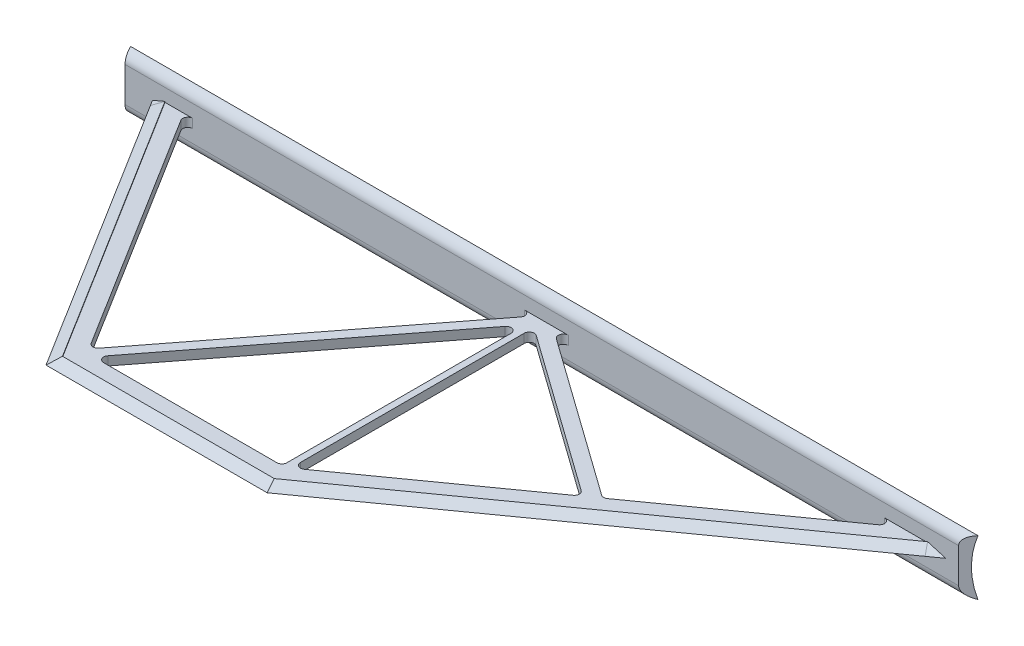
SolidWorks part; units mm, degrees
material "6061-T6 (SS)"
ref_plane "Front Plane" through (0, 0, 0) normal (0, 0, 1) x (1, 0, 0)
ref_plane "Top Plane" through (0, 0, 0) normal (0, 1, 0) x (1, 0, 0)
ref_plane "Right Plane" through (0, 0, 0) normal (1, 0, 0) x (0, 0, -1)
sketch "CS path" plane through (0, 0, 0) normal (0, 1, 0) x (1, 0, 0)
  line L0 (-228.6, 0) -> (228.6, 0) construction
  line L1 (-63.5, -163.068) -> (0, 0) construction
  line L2 (0, -163.068) -> (228.6, 0)
  line L3 (-228.6, 0) -> (-242.0318, 21.558) construction
  line L4 (228.6, 0) -> (290.6344, 44.2512) construction
  line L5 (228.6, 0) -> (290.6344, 44.2512)
  line L6 (-127, -163.068) -> (0, -163.068)
  line L8 (-228.6, 0) -> (-242.0318, 21.558)
  line L9 (-127, -163.068) -> (-228.6, 0) construction
  line L12 (-127, -163.068) -> (-228.6, 0)
  dimension "D1" = 163.068
  dimension "D2" = 127
  dimension "D3" = 457.2
  dimension "D4" = 228.6
  dimension "D5" = 0
  dimension "D6" = 25.4
  dimension "D7" = 76.2
sketch "Sketch8" plane through (0, 0, 0) normal (1, 0, 0) x (0, 0, -1)
  line L0 (0, 0) -> (82.804, 0) construction
  line L1 (82.804, 0) -> (-43.02, 26.7447) construction
  line L2 (82.804, 0) -> (-44.9942, -27.1644) construction
  line L3 (4.8299, 16.5739) -> (0, 17.6005)
  line L4 (4.8299, -16.5739) -> (0, -17.6005)
  line L5 (0, 17.6005) -> (0, -17.6005)
  line L6 (3.175, 0) -> (86.995, 0) construction
  arc A0 (4.8299, 16.5739) -> (4.8299, -16.5739) centre (86.995, 0) ccw
  dimension "D1" = 12
  dimension "D2" = 12
extrude "Boss-Extrude3" add sketch "Sketch8" along normal blind 254 and the other way blind 254 separate body
ref_plane "Plane7" through (0, 17.6005, 0) normal (0, -1, 0) x (1, 0, 0)
ref_plane "Plane8" through (290.6344, 0, -44.2512) normal (0.8141, 0, -0.5807) x (-0.5807, 0, -0.8141)
sketch "Sketch9" plane through (290.6344, 0, -44.2512) normal (0.8141, 0, -0.5807) x (-0.5807, 0, -0.8141)
  line L1 (0, 3.175) -> (9.525, 3.175)
  line L3 (0, -3.175) -> (9.525, -3.175)
  line L4 (9.525, 3.175) -> (9.525, -3.175)
  line L6 (0, 3.175) -> (-6.35, 0)
  line L7 (-6.35, 0) -> (0, -3.175)
  dimension "D3" = 9.525
sweep "Sweep2" add profiles "Sketch9" path "CS path"
sketch "Sketch11" plane through (-254, 0, 0) normal (-1, 0, 0) x (0, 0, 1)
  line L0 (-55.6299, -16.5739) -> (-55.6299, 16.5739)
  line L1 (-4.8299, 16.5739) -> (-55.6299, 16.5739)
  line L2 (-4.8299, -16.5739) -> (-55.6299, -16.5739)
  arc A0 (-4.8299, 16.5739) -> (-4.8299, -16.5739) centre (-86.995, 0) cw
  dimension "D1" = 50.8
extrude "Cut-Extrude1" cut sketch "Sketch11" against normal blind 762
sketch "Sketch12" plane through (0, 3.175, 0) normal (0, 1, 0) x (1, 0, 0)
  line L0 (-3.0491, -153.543) -> (-3.0491, 0) construction
  line L1 (-254, 0) -> (254, 0) construction
  line L2 (-3.0491, 0) -> (-121.7121, -153.543) construction
  line L3 (104.5745, -76.7715) -> (-3.0491, 0) construction
  line L4 (-6.8406, 0) -> (-123.4044, -150.8268)
  line L6 (-1.0491, -152.1163) -> (-1.0491, -6.3401)
  line L7 (-217.3775, 0) -> (-121.7121, -153.543)
  line L8 (-121.7121, -153.543) -> (-3.0491, -153.543)
  line L9 (-3.0491, -153.543) -> (212.1981, 0)
  line L10 (212.1981, 0) -> (-217.3775, 0)
  line L11 (-4.9541, -153.543) -> (-4.9541, -7.3709)
  line L12 (108.0185, -74.3148) -> (3.8388, 0)
  line L13 (101.1305, -79.2282) -> (-1.0491, -6.3401)
  line L14 (106.8974, -73.5151) -> (-0.7262, 3.2564) construction
  line L15 (-5.4229, 1.8345) -> (-124.0858, -151.7085) construction
  line L16 (-4.9541, -7.3709) -> (-117.9206, -153.543)
  line L18 (-1.0491, -153.543) -> (-1.0491, 0) construction
  line L19 (102.2516, -80.0279) -> (-5.372, -3.2564) construction
  line L21 (-4.9541, -153.543) -> (-4.9541, 0) construction
  line M9 (-121.7121, -153.543) -> (-217.3775, 0)
  dimension "D3" = 2
  dimension "D2" = 3
  dimension "D1" = 3
  dimension "D4" = 1.905
  dimension "D5" = 4
  dimension "D6" = 4
extrude "Boss-Extrude4" add sketch "Sketch12" against normal blind 6.35 contours L8 L9 L10 M9 region at (-1.5009, 3.175, 2.7773)
fillet "Fillet3" radius 6.35 2 edges at (0, -17.6005, 0) (0, 17.6005, 0)
ref_plane "Plane9" through (0, 16.5739, 0) normal (0, 1, 0) x (1, 0, 0)
sketch "Sketch13" plane through (0, 16.5739, 0) normal (0, 1, 0) x (1, 0, 0)
  line L0 (-254, 4.8299) -> (-254, 0)
  line L1 (254, 0) -> (-254, 0) construction
  line L2 (-254, 4.8299) -> (-254, 0) construction
  line L3 (-254, 0) -> (-252.5427, 0)
  line L4 (-252.5427, 0) -> (-254, 4.8299)
  line L5 (254, 4.8299) -> (254, 0)
  line L6 (254, 0) -> (247.2036, 0)
  line L7 (247.2036, 0) -> (254, 4.8299)
  line L9 (-130.5253, -169.418) -> (-233.9895, -3.3579) construction
  line L11 (-254, 4.8299) -> (254, 4.8299) construction
  dimension "D1" = 4.8299
  dimension "D2" = 73.21
  dimension "D3" = 54.6
  dimension "D4" = 58.075
extrude "Cut-Extrude2" cut sketch "Sketch13" against normal blind 50.8
sketch "Sketch14" plane through (0, 3.175, 0) normal (0, 1, 0) x (1, 0, 0)
  line L0 (228.6, 0) -> (-228.6, 0)
  line L1 (-228.6, 0) -> (-127, -163.068)
  line L2 (-127, -163.068) -> (0, -163.068)
  line L3 (0, -163.068) -> (228.6, 0)
extrude "Cut-Extrude3" cut sketch "Sketch14" against normal blind 0.508
mirror "Mirror1" about plane through (0, 0, 0) normal (0, 1, 0) of "Cut-Extrude3"
fillet "Fillet4" radius 3 12 edges at (-217.3775, 0, 0) (-123.4044, 0, 150.8268) (-117.9206, 0, 153.543) (-4.9541, 0, 7.3709) (-6.8406, 0, 0) (3.8388, 0, 0) (-1.0491, 0, 6.3401) (-4.9541, 0, 153.543) (-1.0491, 0, 152.1163) (101.1305, 0, 79.2282) (108.0185, 0, 74.3148) (212.1981, 0, 0)
